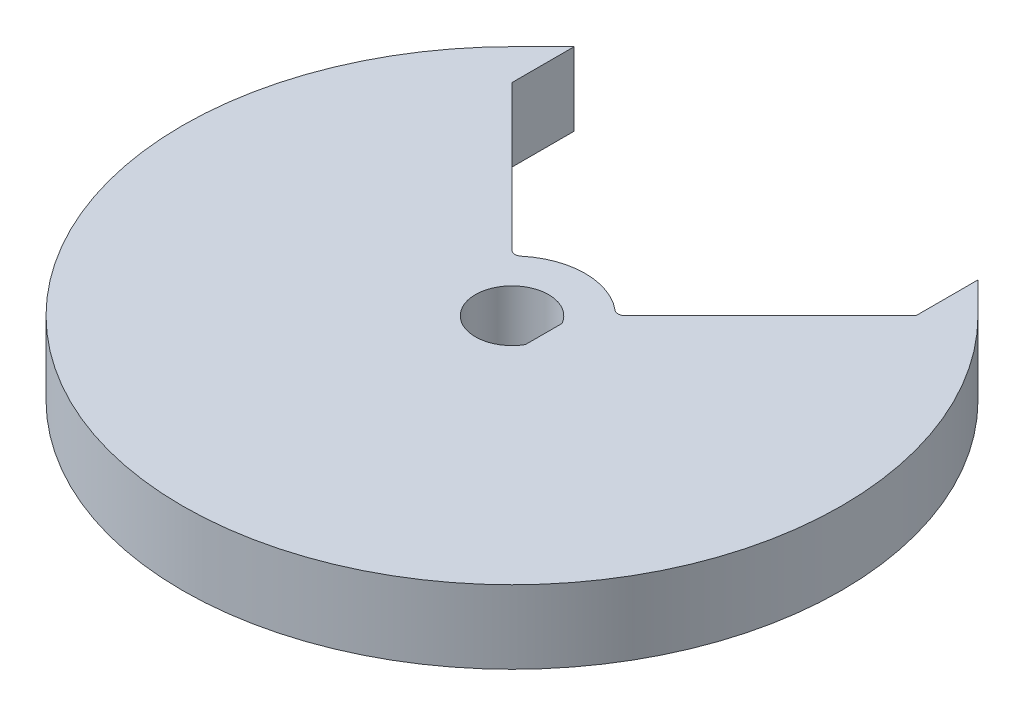
SolidWorks part; units mm, degrees
material "ABS"
ref_plane "Front Plane" through (0, 0, 0) normal (0, 0, 1) x (1, 0, 0)
ref_plane "Top Plane" through (0, 0, 0) normal (0, 1, 0) x (1, 0, 0)
ref_plane "Right Plane" through (0, 0, 0) normal (1, 0, 0) x (0, 0, -1)
sketch "Sketch1" plane through (0, 0, 0) normal (0, 1, 0) x (1, 0, 0)
  line L0 (-31.8198, 31.8198) -> (-7.0711, 7.0711)
  line L1 (7.0711, 7.0711) -> (31.8198, 31.8198)
  line L2 (0, 0) -> (0, 20) construction
  line L3 (0, 0) -> (-7.0711, 7.0711) construction
  line L4 (7.0711, 7.0711) -> (0, 0) construction
  arc A0 (-31.8198, 31.8198) -> (31.8198, 31.8198) centre (0, 0) ccw
  circle A1 centre (0, 0) radius 5
  arc A2 (7.0711, 7.0711) -> (-7.0711, 7.0711) centre (0, 0) ccw
  dimension "D1" = 10
  dimension "D2" = 90
  dimension "D3" = 20
  dimension "D4" = 45
extrude "Boss-Extrude1" add sketch "Sketch1" along normal blind 10
fillet "Fillet1" radius 1 2 edges at (7.0711, 5, -7.0711) (-7.0711, 5, -7.0711)
sketch "Sketch2" plane through (0, 10, 0) normal (0, 1, 0) x (1, 0, 0)
  line L0 (4.3301, 2.5) -> (4.3301, -2.5)
  arc A0 (4.3301, -2.5) -> (4.3301, 2.5) centre (0, 0) ccw
  circle A1 centre (0, 0) radius 5 construction
  dimension "D1" = 5
extrude "Shaft D" add sketch "Sketch2" against normal up to surface (10 mm away) up to face at (0, 0, -3.2457)
sketch "Sketch3" plane through (0, 10, 0) normal (0, 1, 0) x (1, 0, 0)
  line L0 (-31.8198, 31.8198) -> (-27.5772, 36.0624)
  line L1 (-27.5772, 36.0624) -> (-27.5772, 27.5772)
  line L2 (-7.746, 7.746) -> (-31.8198, 31.8198) construction
  line L3 (-27.5772, 27.5772) -> (-31.8198, 31.8198)
  line L4 (0, 0) -> (0, 30.6174) construction
  line L5 (27.5772, 27.5772) -> (31.8198, 31.8198)
  line L6 (27.5772, 36.0624) -> (27.5772, 27.5772)
  line L7 (31.8198, 31.8198) -> (27.5772, 36.0624)
  dimension "D1" = 6
extrude "Boss-Extrude2" add sketch "Sketch3" against normal up to surface (10 mm away) up to face at (0, 0, -3.2457)
